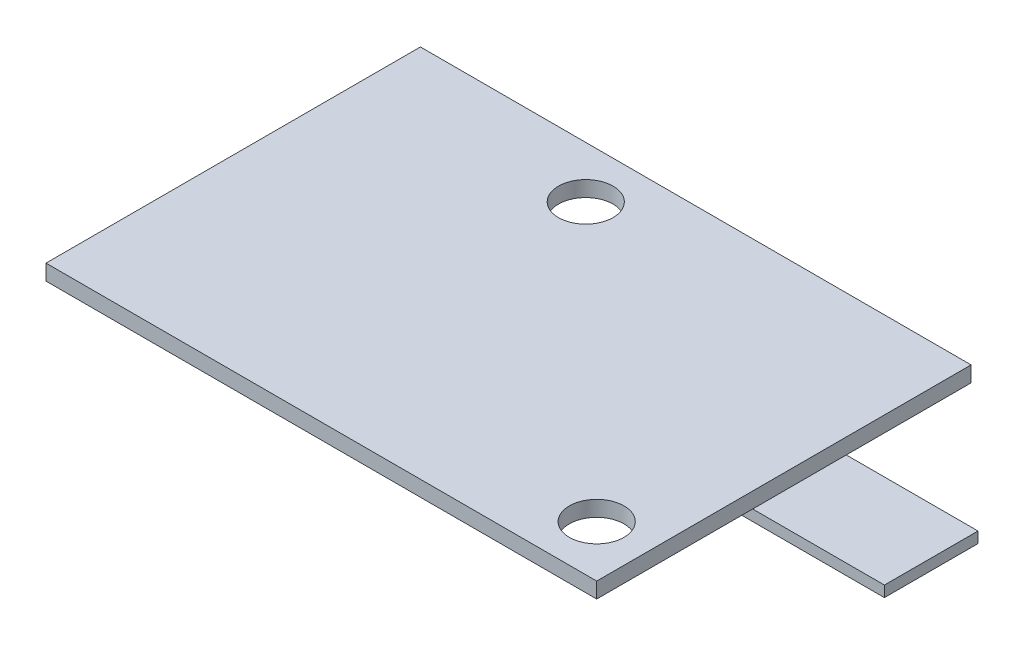
SolidWorks part; units mm, degrees
ref_plane "Спереди" through (0, 0, 0) normal (0, 0, 1) x (1, 0, 0)
ref_plane "Сверху" through (0, 0, 0) normal (0, 1, 0) x (1, 0, 0)
ref_plane "Справа" through (0, 0, 0) normal (1, 0, 0) x (0, 0, -1)
sketch "Sketch1" plane through (0, 0, 0) normal (0, 1, 0) x (1, 0, 0)
  line L1 (-17.65, -12) -> (17.65, -12)
  line L2 (-17.65, -12) -> (-17.65, 12)
  line L3 (-17.65, 12) -> (17.65, 12)
  line L4 (17.65, -12) -> (17.65, 12)
  line L5 (-17.65, -12) -> (17.65, 12) construction
  line L6 (-17.65, 12) -> (17.65, -12) construction
  point P0 (0, 0)
  dimension "D1" = 35.3
  dimension "D2" = 24
extrude "Boss-Extrude1" add sketch "Sketch1" along normal blind 1
hole_wizard "Ø3.5 (3.5) Diameter Hole1" positions "Sketch3" profile "Sketch4" hole size "Ø3.5" standard "ANSI Metric" end condition up to next
sketch "Sketch3" plane through (0, 1, 0) normal (0, 1, 0) x (1, 0, 0)
  line L0 (17.65, 12) -> (-17.65, 12) construction
  line L3 (-17.65, -12) -> (17.65, -12) construction
  line L4 (17.65, -12) -> (17.65, 12) construction
  point P0 (-3.75, 8.7)
  point P2 (14.35, -8.7)
  point P21 (0, 0)
  dimension "D1" = 3.3
  dimension "D2" = 21.4
  dimension "D3" = 3.3
  dimension "D4" = 3.3
sketch "Sketch4" plane through (-3.75, 1, -8.7) normal (1, 0, 0) x (0, 0, 1)
  line L0 (0, 0) -> (0, 1)
  line L1 (0, 1) -> (1.75, 1)
  line L2 (1.75, 1) -> (1.75, 0)
  line L5 (1.75, 0) -> (0, 0)
  line L11 (0, -6.35) -> (0, 107.95) construction
  dimension "Thru Hole Dia." = 3.5
  dimension "Thru Hole Depth" = 1
sketch "Sketch5" plane through (0, 0, 0) normal (0, -1, 0) x (1, 0, 0)
  line L0 (-17.65, 12) -> (17.65, 12) construction
  line L1 (14.8664, 2) -> (26.0926, 2)
  line L2 (14.8664, 2) -> (14.8664, -4)
  line L3 (14.8664, -4) -> (26.0926, -4)
  line L4 (26.0926, 2) -> (26.0926, -4)
  dimension "D1" = 6
  dimension "D2" = 10
extrude "Boss-Extrude2" add sketch "Sketch5" along normal blind 0.7
sketch "Sketch6" plane through (0, 0, 0) normal (0, 1, 0) x (1, 0, 0)
  line L0 (26.0926, 1) -> (50026.0926, 1) construction
  line L1 (26.0926, 4) -> (26.0926, -2) construction
  point P4 (26.0926, 1)
ref_plane "Plane1" through (0, 0, -1) normal (0, 0, 1) x (1, 0, 0)
